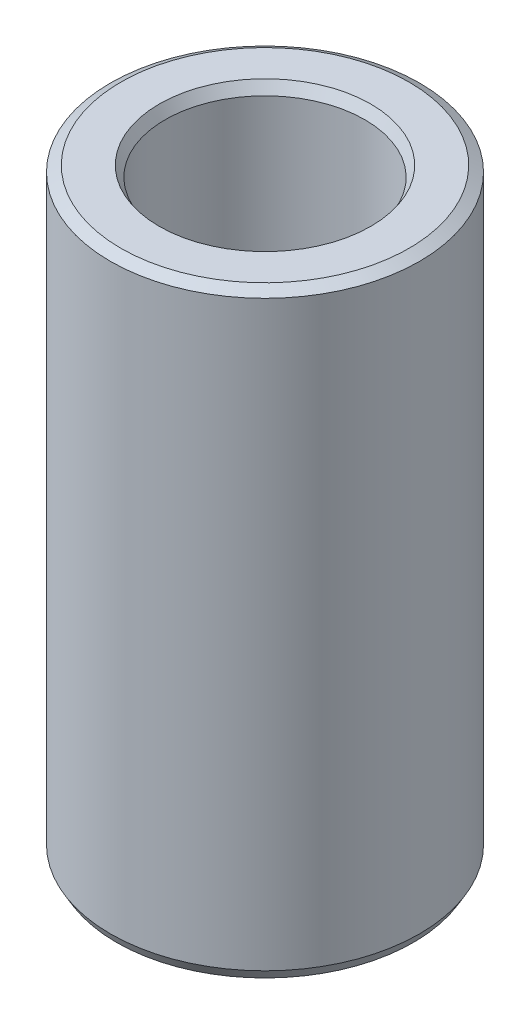
SolidWorks part; units mm, degrees
ref_plane "Front Plane" through (0, 0, 0) normal (0, 0, 1) x (1, 0, 0)
ref_plane "Top Plane" through (0, 0, 0) normal (0, 1, 0) x (1, 0, 0)
ref_plane "Right Plane" through (0, 0, 0) normal (1, 0, 0) x (0, 0, -1)
sketch "Sketch1" plane through (0, 0, 0) normal (0, 1, 0) x (1, 0, 0)
  circle A0 centre (0, 0) radius 60
  dimension "SLEEVE_OD" = 120
extrude "Boss-Extrude1" add sketch "Sketch1" along normal blind 232.5516
sketch "Sketch2" plane through (0, 0, 0) normal (0, 1, 0) x (1, 0, 0)
  circle A0 centre (0, 0) radius 38.7628
  dimension "BORE_D" = 77.5256
extrude "Cut-Extrude1" cut sketch "Sketch2" along normal through all
chamfer "Chamfer1" distance 2.3494 angle 60 4 edges at (0, 232.5516, 38.7628) (0, 0, 38.7628) (0, 0, 60) (0, 232.5516, 60) first distance on face at (0, 232.5516, 38.7628) first distance on face at (0, 0, 38.7628) first distance on face at (0, 232.5516, 60)
